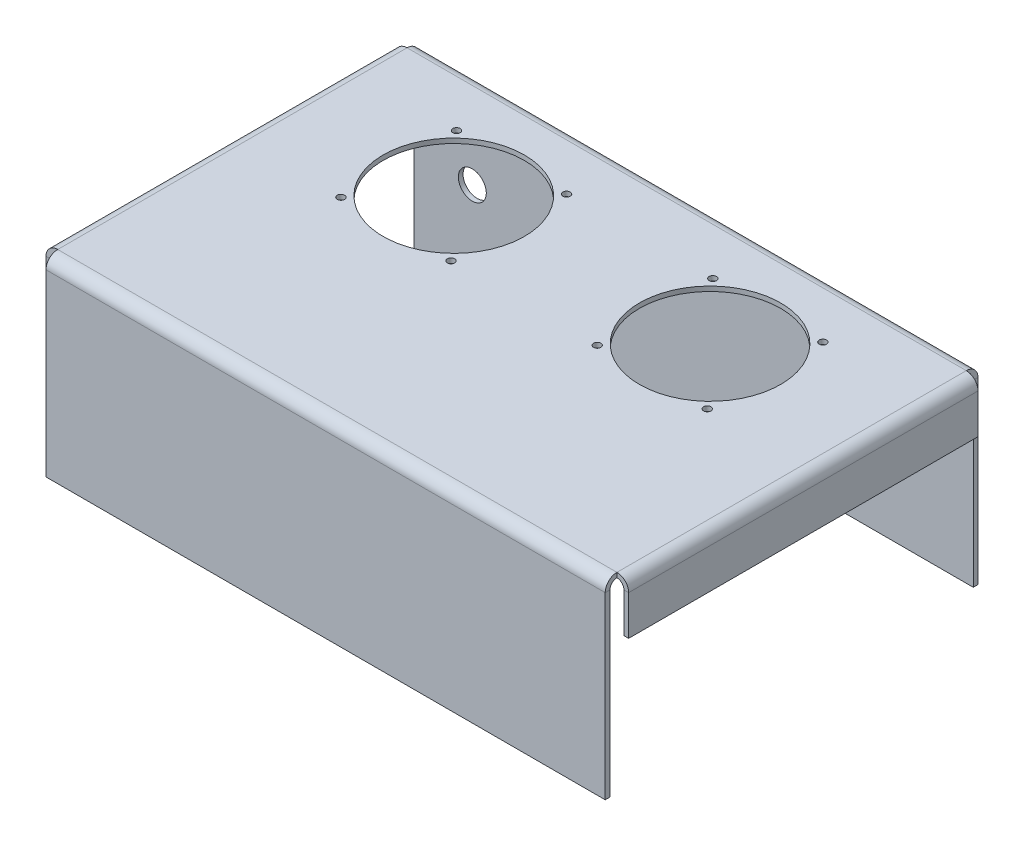
SolidWorks part; units mm, degrees
note: The reader was unsure of these and kept them because the rebuilt part matched: flange length of "Edge-Flange1", "Edge-Flange2".
ref_plane "Front Plane" through (0, 0, 0) normal (0, 0, 1) x (1, 0, 0)
ref_plane "Top Plane" through (0, 0, 0) normal (0, 1, 0) x (1, 0, 0)
ref_plane "Right Plane" through (0, 0, 0) normal (1, 0, 0) x (0, 0, -1)
sketch "Sketch1" plane through (0, 0, 0) normal (0, 1, 0) x (1, 0, 0)
  line L1 (-76.2, -50.8) -> (76.2, -50.8)
  line L2 (-76.2, -50.8) -> (-76.2, 50.8)
  line L3 (-76.2, 50.8) -> (76.2, 50.8)
  line L4 (76.2, -50.8) -> (76.2, 50.8)
  line L5 (-76.2, -50.8) -> (76.2, 50.8) construction
  line L6 (-76.2, 50.8) -> (76.2, -50.8) construction
  point P0 (0, 0)
  dimension "D1" = 152.4
  dimension "D2" = 101.6
base flange "Base-Flange1" sketch "Sketch1" thickness 1.2903 reverse thickness direction no parameters "D1"=1.905
edge flange "Edge-Flange1" sketch "Sketch14" flange profiles "Sketch14", "Sketch15" flange angle 90 flange length 50.8 flange position material inside bend radius 1.905 thickness 1.2903 relief rectangular parameters "D6"=10, "D8"=0.254
sketch "Sketch14" plane through (0, -1.2903, 50.8) normal (0, 0, 1) x (-1, 0, 0)
  line L0 (76.2, 0) -> (-76.2, 0) construction
  line L1 (76.2, 0) -> (-76.2, 0)
  line L2 (-76.2, 0) -> (-76.2, 50.8)
  line L3 (-76.2, 50.8) -> (76.2, 50.8)
  line L4 (76.2, 50.8) -> (76.2, 0)
sketch "Sketch15" plane through (0, -1.2903, -50.8) normal (0, 0, -1) x (1, 0, 0)
  line L0 (76.2, 0) -> (-76.2, 0) construction
  line L1 (76.2, 0) -> (-76.2, 0)
  line L2 (-76.2, 0) -> (-76.2, 50.8)
  line L3 (-76.2, 50.8) -> (76.2, 50.8)
  line L4 (76.2, 50.8) -> (76.2, 0)
bend "EdgeBend1" bend radius 1.905 bend angle 90 parameters "D5"=1
bend "EdgeBend2" bend radius 1.905 bend angle 90 parameters "D5"=2
edge flange "Edge-Flange2" sketch "Sketch20" flange profiles "Sketch20", "Sketch21" flange angle 90 flange length 12.7 flange position bend outside bend radius 1.905 thickness 1.2903 relief rectangular parameters "D6"=10, "D8"=0.254
sketch "Sketch20" plane through (-76.2, -1.2903, 0) normal (-1, 0, 0) x (0, 0, -1)
  line L2 (-47.6047, 0) -> (-47.6047, 12.7)
  line L3 (-47.6047, 12.7) -> (47.6047, 12.7)
  line L4 (47.6047, 12.7) -> (47.6047, 0)
  line L9 (47.6047, 0) -> (-47.6047, 0) construction
  line L10 (47.6047, 0) -> (-47.6047, 0)
sketch "Sketch21" plane through (76.2, -1.2903, 0) normal (1, 0, 0) x (0, 0, 1)
  line L2 (-47.6047, 0) -> (-47.6047, 12.7)
  line L3 (-47.6047, 12.7) -> (47.6047, 12.7)
  line L4 (47.6047, 12.7) -> (47.6047, 0)
  line L7 (47.6047, 0) -> (-47.6047, 0) construction
  line L8 (47.6047, 0) -> (-47.6047, 0)
bend "EdgeBend3" bend radius 1.905 bend angle 90 parameters "D5"=3
bend "EdgeBend4" bend radius 1.905 bend angle 90 parameters "D5"=4
sketch "Sketch22" plane through (0, 0, 0) normal (0, 1, 0) x (1, 0, 0)
  line L0 (0, 0) -> (0, 111.9378) construction
  line L3 (-65.175, 42.55) -> (-65.175, -4.45) construction
  line L4 (4.675, 42.55) -> (65.175, 42.55) construction
  line L5 (4.675, 42.55) -> (4.675, -4.45) construction
  line L6 (4.675, -4.45) -> (65.175, -4.45) construction
  line L7 (65.175, 42.55) -> (65.175, -4.45) construction
  line L8 (-4.675, -4.45) -> (-65.175, -4.45) construction
  line L9 (-4.675, 42.55) -> (-4.675, -4.45) construction
  line L10 (-4.675, 42.55) -> (-65.175, 42.55) construction
  line L11 (65.175, 42.55) -> (-65.175, 42.55) construction
  line L12 (4.675, 42.55) -> (-125.675, 42.55) construction
  line L14 (-65.175, 42.55) -> (-65.175, 172.9) construction
  line L15 (4.675, 42.55) -> (65.175, -4.45) construction
  line L16 (76.2, 50.8) -> (-76.2, 50.8) construction
  line L18 (65.175, 42.55) -> (4.675, -4.45) construction
  line L20 (19.925, 3.3) -> (49.925, 3.3) construction
  line L21 (19.925, 3.3) -> (19.925, 34.8) construction
  line L22 (19.925, 34.8) -> (49.925, 34.8) construction
  line L23 (49.925, 3.3) -> (49.925, 34.8) construction
  line L24 (19.925, 3.3) -> (49.925, 34.8) construction
  line L25 (19.925, 34.8) -> (49.925, 3.3) construction
  circle A0 centre (34.925, 19.05) radius 19.25
  circle A1 centre (19.925, 34.8) radius 1
  circle A2 centre (49.925, 34.8) radius 1
  circle A3 centre (49.925, 3.3) radius 1
  circle A4 centre (19.925, 3.3) radius 1
  circle A5 centre (-19.925, 3.3) radius 1
  circle A6 centre (-49.925, 3.3) radius 1
  circle A7 centre (-49.925, 34.8) radius 1
  circle A8 centre (-19.925, 34.8) radius 1
  circle A9 centre (-34.925, 19.05) radius 19.25
  dimension "D3" = 38.5
  dimension "D6" = 2
  dimension "D7" = 31.75
  dimension "D1" = 60.5
  dimension "D2" = 47
  dimension "D4" = 30
  dimension "D5" = 31.5
  dimension "D8" = 69.85
extrude "Cut-Extrude1" cut sketch "Sketch22" against normal blind 2.54 contours A9
sketch "Sketch23" plane through (0, 0, -50.8) normal (0, 0, -1) x (-1, 0, 0)
  line L0 (60.325, -25.4) -> (-60.325, -25.4) construction
  line L1 (0, -25.4) -> (0, 0) construction
  line L2 (-76.2, 0) -> (76.2, 0) construction
  circle A0 centre (60.325, -25.4) radius 3.81
  circle A1 centre (-60.325, -25.4) radius 3.81
  dimension "D1" = 7.62
  dimension "D2" = 120.65
  dimension "D3" = 25.4
extrude "Cut-Extrude2" cut sketch "Sketch23" against normal up to next normal cut yes
sketch "Bend-Lines1" plane through (0, 0, 0) normal (0, 1, 0) x (1, 0, 0)
sketch "Bounding-Box1" plane through (0, 0, 0) normal (0, 1, 0) x (1, 0, 0)
sheet metal parameters "Sheet-Metal(1)" thickness 1.2903 parameters "D1"=1.905
flat pattern "Flat-Pattern(1)" [suppressed]
sketch "Bend-Lines2" plane through (0, 0, 0) normal (0, 1, 0) x (1, 0, 0)
sketch "Bounding-Box2" [suppressed] plane through (0, 0, 0) normal (0, 1, 0) x (1, 0, 0)
sheet metal parameters "Sheet-Metal(2)" thickness 1.2903 parameters "D1"=1.905
flat pattern "Flat-Pattern(1)" [suppressed]
sketch "Bend-Lines2" plane through (0, 0, 0) normal (0, 1, 0) x (1, 0, 0)
sketch "Bounding-Box2" [suppressed] plane through (0, 0, 0) normal (0, 1, 0) x (1, 0, 0)
bend of the flat pattern "Flatten-<EdgeBend1>1"
bend of the flat pattern "Flatten-<EdgeBend2>1"
sheet metal parameters "Sheet-Metal(3)" thickness 1.2903 parameters "D1"=1.905
flat pattern "Flat-Pattern(1)" [suppressed]
sketch "Bend-Lines2" plane through (0, 0, 0) normal (0, 1, 0) x (1, 0, 0)
sketch "Bounding-Box2" [suppressed] plane through (0, 0, 0) normal (0, 1, 0) x (1, 0, 0)
bend of the flat pattern "Flatten-<EdgeBend1>1"
bend of the flat pattern "Flatten-<EdgeBend2>1"
bend of the flat pattern "Flatten-<EdgeBend3>1"
bend of the flat pattern "Flatten-<EdgeBend4>1"
sheet metal parameters "Sheet-Metal(4)" thickness 1.2903 parameters "D1"=1.905
flat pattern "Flat-Pattern(1)" [suppressed]
sketch "Bend-Lines2" plane through (0, 0, 0) normal (0, 1, 0) x (1, 0, 0)
sketch "Bounding-Box2" [suppressed] plane through (0, 0, 0) normal (0, 1, 0) x (1, 0, 0)
bend of the flat pattern "Flatten-<EdgeBend1>1"
bend of the flat pattern "Flatten-<EdgeBend2>1"
bend of the flat pattern "Flatten-<EdgeBend3>1"
bend of the flat pattern "Flatten-<EdgeBend4>1"
sheet metal parameters "Sheet-Metal(5)" thickness 1.2903 parameters "D1"=1.905
flat pattern "Flat-Pattern(1)" [suppressed]
sketch "Bend-Lines2" plane through (0, 0, 0) normal (0, 1, 0) x (1, 0, 0)
sketch "Bounding-Box2" [suppressed] plane through (0, 0, 0) normal (0, 1, 0) x (1, 0, 0)
bend of the flat pattern "Flatten-<EdgeBend1>1"
bend of the flat pattern "Flatten-<EdgeBend2>1"
bend of the flat pattern "Flatten-<EdgeBend3>1"
bend of the flat pattern "Flatten-<EdgeBend4>1"
